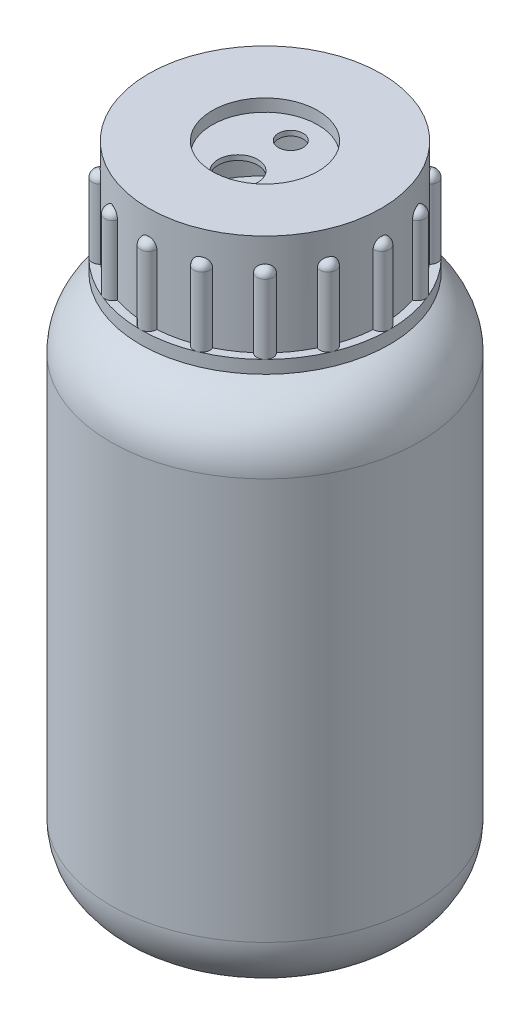
SolidWorks part; units mm, degrees
material "ABS PC"
ref_plane "Front Plane" through (0, 0, 0) normal (0, 0, 1) x (1, 0, 0)
ref_plane "Top Plane" through (0, 0, 0) normal (0, 1, 0) x (1, 0, 0)
ref_plane "Right Plane" through (0, 0, 0) normal (1, 0, 0) x (0, 0, -1)
sketch "Sketch1" plane through (0, 0, 0) normal (0, 0, 1) x (1, 0, 0)
  line L0 (0, 0) -> (0, 127.5) construction
  line L1 (0, 0) -> (-19.125, 0)
  line L2 (-31.125, 12) -> (-31.125, 92.9692)
  line L3 (-21.2088, 104.7869) -> (-20, 105)
  line L4 (-20, 105) -> (-20, 107)
  line L5 (-20, 107) -> (-23.5, 107)
  line L6 (-23.5, 107) -> (-23.5, 130)
  line L7 (-23.5, 130) -> (-10.65, 130)
  line L8 (-10.65, 130) -> (-10.65, 127.5)
  line L9 (-10.65, 127.5) -> (0, 127.5)
  arc A0 (-19.125, 0) -> (-31.125, 12) centre (-19.125, 12) cw
  arc A1 (-31.125, 92.9692) -> (-21.2088, 104.7869) centre (-19.125, 92.9692) cw
  dimension "D3" = 12
  dimension "D4" = 12
  dimension "D1" = 62.25
  dimension "D2" = 105
  dimension "D5" = 80
  dimension "D6" = 40
  dimension "D7" = 130
  dimension "D8" = 23
  dimension "D9" = 47
  dimension "D10" = 21.3
  dimension "D11" = 2.5
revolve "Revolve-Thin1" add sketch "Sketch1" angle 360 about L0
sketch "Sketch2" plane through (0, 0, 0) normal (1, 0, 0) x (0, 0, -1)
  line L0 (-23.5, 107) -> (-25.125, 107)
  line L1 (-25.125, 107) -> (-25.125, 109.6)
  line L2 (-25.125, 109.6) -> (-23.5, 109.6)
  line L3 (-23.5, 130) -> (-23.5, 107) construction
  line L4 (-23.5, 109.6) -> (-23.5, 107)
  line L5 (0, 130) -> (0, 97.4747) construction
  line L6 (23.5, 130) -> (-23.5, 130) construction
  dimension "D1" = 50.25
  dimension "D2" = 2.6
revolve "Revolve1" add sketch "Sketch2" angle 360 about L5
sketch "Sketch3" plane through (0, 109.6, 0) normal (0, 1, 0) x (1, 0, 0)
  arc A0 (1.624, 23.4438) -> (-1.624, 23.4438) centre (0, 23.5) ccw
  circle A1 centre (0, 0) radius 23.5 construction
  circle A2 centre (0, 0) radius 25.125 construction
  circle A3 centre (0, 0) radius 23.5 construction
  arc A4 (1.624, 23.4438) -> (-1.624, 23.4438) centre (0, 0) ccw
extrude "Extrude1" add sketch "Sketch3" along normal blind 15.5
fillet "Fillet1" radius 1.5 1 edges at (0, 125.1, -25.125)
pattern_circular "CirPattern1" count 16 over 360 about axis through (0, 0, 0) along (0, 1, 0) of "Extrude1", "Fillet1"
sketch "Sketch4" plane through (0, 127.5, 0) normal (0, 1, 0) x (1, 0, 0)
  circle A0 centre (0, -5.4517) radius 4
  circle A1 centre (0, 5.1982) radius 2.5
  dimension "D1" = 5
  dimension "D2" = 8
extrude "Extrude2" cut sketch "Sketch4" against normal blind 15.5
